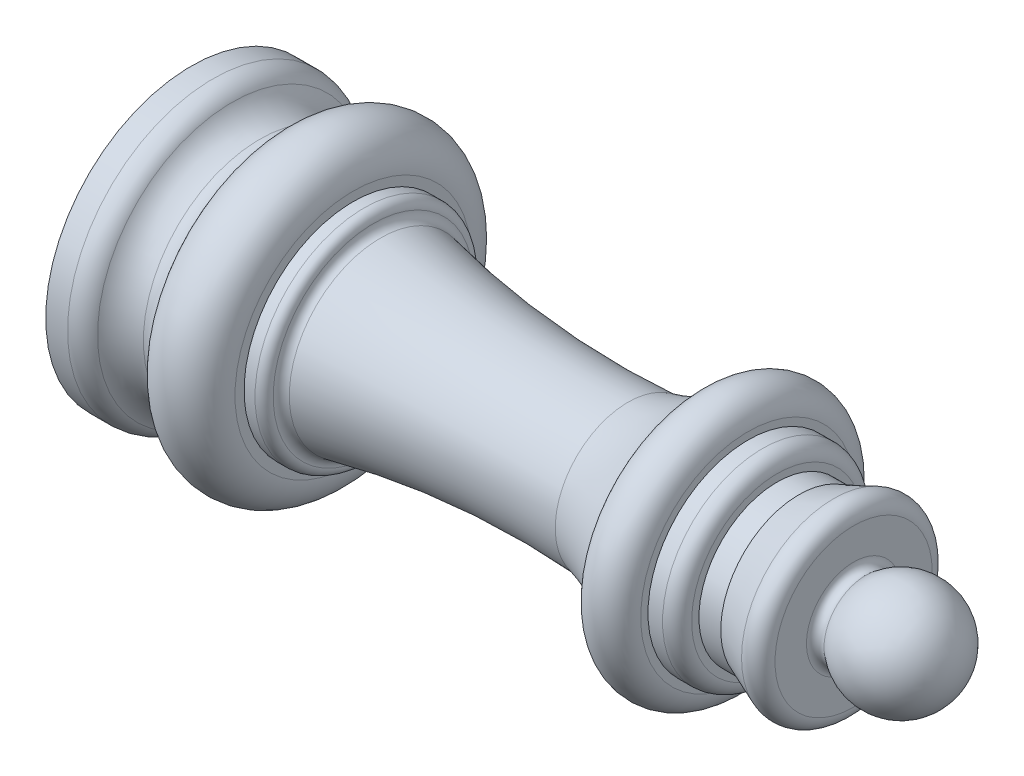
SolidWorks part; units mm, degrees
ref_plane "前基準面" through (0, 0, 0) normal (0, 0, 1) x (1, 0, 0)
ref_plane "上基準面" through (0, 0, 0) normal (0, 1, 0) x (1, 0, 0)
ref_plane "右基準面" through (0, 0, 0) normal (1, 0, 0) x (0, 0, -1)
sketch "草圖1" plane through (0, 0, 0) normal (0, 0, 1) x (1, 0, 0)
  line L0 (0, 0) -> (-114.0071, 0) construction
  line L3 (-14.0088, 6.4733) -> (-14.0088, 13.75)
  line L4 (-14.0088, 13.75) -> (-21.5088, 10.75)
  line L5 (-21.5088, 10.75) -> (-24.5088, 10.75)
  line L6 (-24.5088, 10.75) -> (-24.5088, 13.75)
  line L10 (-105, 0) -> (-105, 20)
  line L11 (-105, 20) -> (-102, 20)
  line L12 (0, 0) -> (-105, 0)
  line L14 (-82.75, 15) -> (-82.75, 16.25)
  line L16 (-82.75, 15) -> (-81.25, 15)
  line L20 (-24.5088, 13.75) -> (-28.5088, 13.75)
  line L25 (-28.5088, 13.75) -> (-28.5088, 14.75)
  arc A0 (-45, 10) -> (-79.0118, 12.5277) centre (-52.8282, 134.7546) cw
  arc A1 (-99.3958, 18.4893) -> (-102, 20) centre (-102, 17) ccw
  arc A3 (-80, 13.75) -> (-81.25, 15) centre (-81.25, 13.75) ccw
  arc A4 (-80, 13.75) -> (-79.0118, 12.5277) centre (-78.75, 13.75) ccw
  arc A5 (-82.75, 16.25) -> (-92.4492, 17.9581) centre (-87.75, 16.25) ccw
  arc A7 (-99.3958, 18.4893) -> (-95.5887, 16) centre (-95.0554, 20.9715) ccw
  arc A8 (-92.4492, 17.9581) -> (-95.5887, 16) centre (-95.2687, 18.9829) cw
  arc A9 (0, 0) -> (-12.3607, 5.7117) centre (-7.5, 0) ccw
  arc A10 (-14.0088, 6.4733) -> (-12.3607, 5.7117) centre (-13.0088, 6.4733) ccw
  arc A12 (-28.5088, 14.75) -> (-35.5, 14.5) centre (-32, 14.5022) ccw
  arc A13 (-35.5, 14.5) -> (-45, 10) centre (-50.4939, 33.8761) cw
  point P4 (-32.1251, 18)
  point P26 (-99, 20)
  dimension "D14" = 125
  dimension "D18" = 32
  dimension "D17" = 3
  dimension "D20" = 25
  dimension "D22" = 1.25
  dimension "D21" = 1.25
  dimension "D24" = 1.25
  dimension "D25" = 32.5
  dimension "D11" = 5
  dimension "D15" = 5
  dimension "D12" = 3
  dimension "D33" = 45
  dimension "D28" = 15
  dimension "D31" = 24.5
  dimension "D4" = 1
  dimension "D36" = 7
  dimension "D6" = 36
  dimension "D3" = 27.5
  dimension "D5" = 3
  dimension "D7" = 7.5
  dimension "D8" = 105
  dimension "D9" = 4
  dimension "D10" = 21.5
  dimension "D13" = 40
  dimension "D16" = 3
  dimension "D19" = 40
  dimension "D23" = 27.5
  dimension "D26" = 1.5
  dimension "D27" = 30
  dimension "D29" = 35.5
  dimension "D30" = 27.5
  dimension "D32" = 6
  dimension "D34" = 20
  dimension "D35" = 14.5
  dimension "D37" = 1
revolve "旋轉1" add sketch "草圖1" angle 360 about L0
revolve "旋轉3" add sketch "草圖1<3>" angle 360 about L0
sketch "草圖1<3>" plane through (0, 0, 0) normal (0, 0, 1) x (1, 0, 0) same geometry as "草圖1"
fillet "圓角1" radius 2 3 edges at (-24.5088, 0, -13.75) (-14.0088, 0, -13.75) (-35.5, 0, -14.5)
